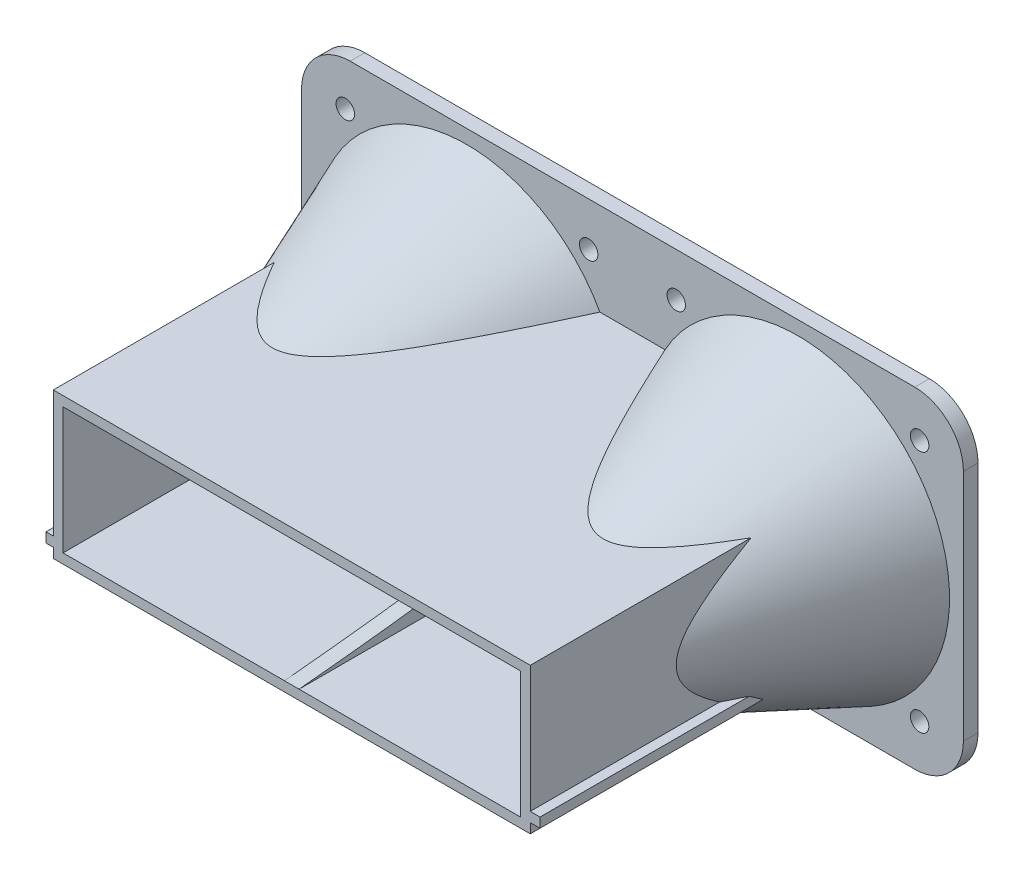
SolidWorks part; units mm, degrees
ref_plane "Plan de face" through (0, 0, 0) normal (0, 0, 1) x (1, 0, 0)
ref_plane "Plan de dessus" through (0, 0, 0) normal (0, 1, 0) x (1, 0, 0)
ref_plane "Plan de droite" through (0, 0, 0) normal (1, 0, 0) x (0, 0, -1)
sketch "Esquisse1" plane through (0, 0, 0) normal (0, 0, 1) x (1, 0, 0)
  line L0 (-34, 0) -> (6.1017, 40.1017) construction
  line L1 (-68, 34) -> (68, 34)
  line L2 (-68, 34) -> (-68, -34)
  line L3 (-68, -34) -> (68, -34)
  line L4 (68, 34) -> (68, -34)
  line L5 (-34, 0) -> (-77.3126, 43.3126) construction
  line L6 (-34, 0) -> (-74.1631, -40.1631) construction
  line L7 (-34, 0) -> (0, -34) construction
  line L8 (34, 0) -> (66.0797, 32.0797) construction
  line L9 (34, 0) -> (-8.5759, 42.5759) construction
  line L10 (34, 0) -> (74.2164, -40.2164) construction
  line L11 (34, 0) -> (-0.0911, -34.0911) construction
  circle A0 centre (-34, 0) radius 29
  circle A1 centre (34, 0) radius 29
  circle A2 centre (-9, 25) radius 1.9
  circle A3 centre (-59, 25) radius 1.9
  circle A4 centre (-59, -25) radius 1.9
  circle A5 centre (-9, -25) radius 1.9
  circle A6 centre (9, 25) radius 1.9
  circle A7 centre (59, 25) radius 1.9
  circle A8 centre (59, -25) radius 1.9
  circle A9 centre (9, -25) radius 1.9
  dimension "D1" = 58
  dimension "D2" = 58
  dimension "D16" = 3.8
  dimension "D17" = 3.8
  dimension "D18" = 3.8
  dimension "D19" = 3.8
  dimension "D29" = 3.8
  dimension "D30" = 3.8
  dimension "D31" = 3.8
  dimension "D26" = 3.8
  dimension "D3" = 68
  dimension "D4" = 34
  dimension "D5" = 45
  dimension "D6" = 90
  dimension "D7" = 90
  dimension "D8" = 90
  dimension "D9" = 90
  dimension "D10" = 45
  dimension "D11" = 50
  dimension "D12" = 25
  dimension "D13" = 50
  dimension "D14" = 25
  dimension "D15" = 50
  dimension "D20" = 34
  dimension "D21" = 68
  dimension "D22" = 34
  dimension "D23" = 34
  dimension "D24" = 50
  dimension "D25" = 25
  dimension "D27" = 50
  dimension "D28" = 50
extrude "Extrusion1" add sketch "Esquisse1" along normal blind 3
sketch "Esquisse2" plane through (0, 0, 0) normal (0, 1, 0) x (1, 0, 0)
  line L0 (-34, 5.4489) -> (-34, -61.8595) construction
  line L1 (-63, -3) -> (-46.843, -43)
  line L6 (68, -3) -> (-68, -3) construction
  line L7 (-46.843, -43) -> (-49, -43)
  line L8 (-49, -43) -> (-65.157, -3)
  line L9 (-65.157, -3) -> (-63, -3)
  dimension "D1" = 34
  dimension "D2" = 58
  dimension "D3" = 30
  dimension "D5" = 2
  dimension "D7" = 40
revolve "Révolution1" add sketch "Esquisse2" angle 360 about L0
sketch "Esquisse3" plane through (0, 0, 0) normal (0, 1, 0) x (1, 0, 0)
  line L0 (34, 6.0664) -> (34, -55.7698) construction
  line L1 (65.157, -3) -> (49, -43)
  line L2 (68, -3) -> (-68, -3) construction
  line L3 (49, -43) -> (46.843, -43)
  line L4 (46.843, -43) -> (63, -3)
  line L5 (63, -3) -> (65.157, -3)
  dimension "D1" = 34
  dimension "D2" = 2
  dimension "D3" = 58
  dimension "D4" = 40
  dimension "D5" = 30
revolve "Révolution2" add sketch "Esquisse3" angle 360 about L0
sketch "Esquisse4" plane through (0, 0, 43) normal (0, 0, 1) x (1, 0, 0)
  line L1 (-49, 15) -> (49, 15)
  line L2 (-49, 15) -> (-49, -15)
  line L3 (-49, -15) -> (49, -15)
  line L4 (49, 15) -> (49, -15)
  dimension "D1" = 98
  dimension "D2" = 30
  dimension "D3" = 15
  dimension "D4" = 49
extrude "Extrusion2" add sketch "Esquisse4" along normal blind 30 and the other way blind 40
sketch "Esquisse5" plane through (0, 0, 3) normal (0, 0, -1) x (-1, 0, 0)
  circle A0 centre (34, 0) radius 29
extrude "Extrusion3" cut sketch "Esquisse5" against normal blind 40 draft 22
sketch "Esquisse6" plane through (0, 0, 3) normal (0, 0, -1) x (-1, 0, 0)
  circle A0 centre (-34, 0) radius 29
extrude "Extrusion4" cut sketch "Esquisse6" against normal blind 40 draft 22
sketch "Esquisse7" plane through (0, 0, 73) normal (0, 0, 1) x (1, 0, 0)
  line L0 (-6.6914, 15) -> (-49, 15) construction
  line L1 (-47, 13) -> (47, 13)
  line L2 (-47, 13) -> (-47, -13)
  line L3 (-47, -13) -> (47, -13)
  line L4 (47, 13) -> (47, -13)
  line L5 (-49, 15) -> (-49, -15) construction
  dimension "D1" = 2
  dimension "D2" = 26
  dimension "D3" = 2
  dimension "D4" = 94
extrude "Extrusion5" cut sketch "Esquisse7" against normal blind 70
sketch "Esquisse8" plane through (0, 0, 73) normal (0, 0, 1) x (1, 0, 0)
  line L0 (-49, 15) -> (-49, -15) construction
  line L1 (-49, -13) -> (-50.5, -13)
  line L2 (-49, -13) -> (-49, -11)
  line L3 (-49, -11) -> (-50.5, -11)
  line L4 (-50.5, -13) -> (-50.5, -11)
  line L5 (49, -15) -> (49, 15) construction
  line L6 (49, -13) -> (51, -13)
  line L7 (49, -13) -> (49, -11)
  line L8 (49, -11) -> (51, -11)
  line L9 (51, -13) -> (51, -11)
  dimension "D1" = 1.5
  dimension "D2" = 2
  dimension "D3" = 2
  dimension "D4" = 2
extrude "Extrusion6" add sketch "Esquisse8" against normal up to next
fillet "Congé1" radius 10 4 edges at (68, 34, 1.5) (-68, -34, 1.5) (-68, 34, 1.5) (68, -34, 1.5)
sketch "Esquisse9" plane through (0, 0, 0) normal (1, 0, 0) x (0, 0, -1)
  line L3 (-3, -24) -> (-3, 24) construction
  line L4 (-3, 13) -> (-73, 13)
  line L5 (-73, -13) -> (-3, -13)
  line L7 (-3, 31.157) -> (-3, -31.157) construction
  line L8 (0, 0) -> (-82.8409, 0) construction
  line L9 (-11, 7.2145) -> (-11, -8.2767) construction
  line L10 (-3, -13) -> (-3, 13)
  spline S0 degree 2 poles (-73, 13) (51.0004, -1.0175) (-73, -13) knots 0 0 0 1 1 1
  dimension "D1" = 11
extrude "Extrusion7" add sketch "Esquisse9" along normal blind 1.5 and the other way blind 1.5
fillet "Congé7" radius 12 2 edges at (1.5, 0, 3) (-1.5, 0, 3)
